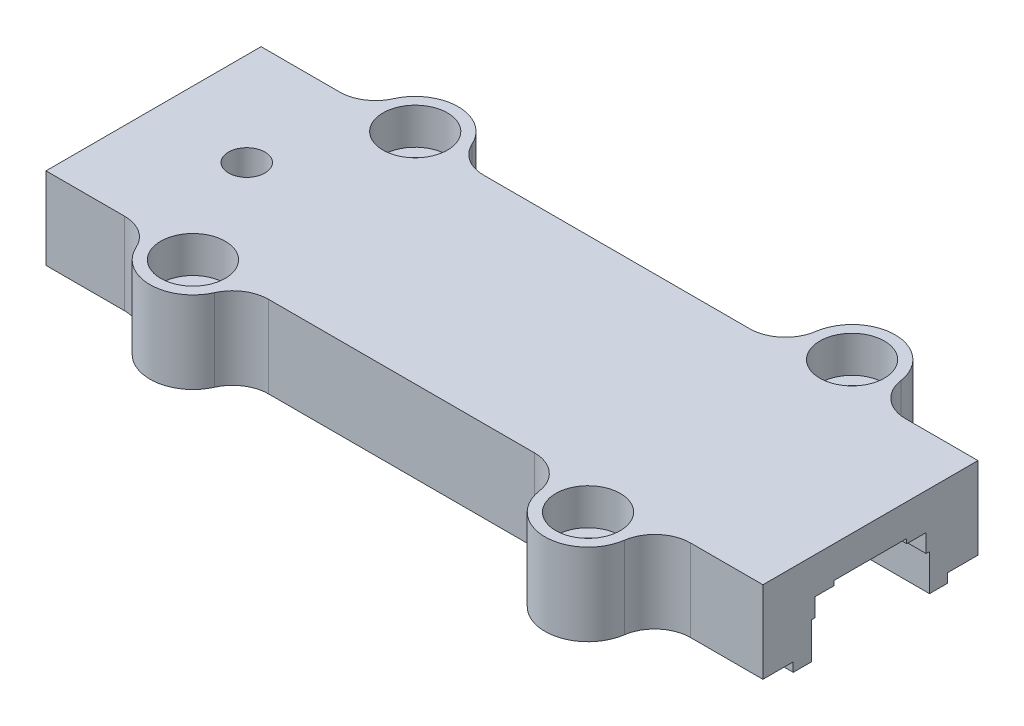
SolidWorks part; units mm, degrees
ref_plane "Front Plane" through (0, 0, 0) normal (0, 0, 1) x (1, 0, 0)
ref_plane "Top Plane" through (0, 0, 0) normal (0, 1, 0) x (1, 0, 0)
ref_plane "Right Plane" through (0, 0, 0) normal (1, 0, 0) x (0, 0, -1)
sketch "Sketch1" plane through (0, 0, 0) normal (0, 1, 0) x (1, 0, 0)
  line L1 (0, 15) -> (100, 15)
  line L2 (0, 15) -> (0, -15)
  line L3 (0, -15) -> (100, -15)
  line L4 (100, 15) -> (100, -15)
  point P4 (0, 0)
  dimension "D1" = 30
  dimension "D2" = 100
extrude "Boss-Extrude1" add sketch "Sketch1" along normal blind 12.7
sketch "Sketch2" plane through (100, 0, 0) normal (1, 0, 0) x (0, 0, -1)
  line L1 (-7.6, 0) -> (7.6, 0)
  line L2 (-7.6, 0) -> (-7.6, 7.62)
  line L3 (-7.6, 7.62) -> (7.6, 7.62)
  line L4 (7.6, 0) -> (7.6, 7.62)
  point P4 (0, 0)
  dimension "D1" = 15.2
  dimension "D2" = 7.62
extrude "Cut-Extrude1" cut sketch "Sketch2" against normal through all
sketch "Sketch3" plane through (100, 0, 0) normal (1, 0, 0) x (0, 0, -1)
  line L1 (-15, 0) -> (-7.6, 0) construction
  line L2 (7.6, 0) -> (15, 0) construction
  line L3 (-7.6, 0) -> (-8.235, 0)
  line L10 (7.6, 0) -> (7.6, 7.62) construction
  line L12 (7.6, 7.62) -> (-7.6, 7.62) construction
  line L13 (-7.6, 0) -> (-8.235, 0)
  line L14 (-7.6, 0) -> (-7.6, 5.08)
  line L15 (-7.6, 5.08) -> (-8.235, 5.08)
  line L16 (-8.235, 0) -> (-8.235, 5.08)
  line L17 (-7.6, 7.62) -> (-7.6, 0) construction
  line L18 (7.6, 0) -> (8.235, 0)
  line L19 (7.6, 0) -> (7.6, 5.08)
  line L20 (7.6, 5.08) -> (8.235, 5.08)
  line L21 (8.235, 0) -> (8.235, 5.08)
  line L22 (-5.06, 7.62) -> (5.06, 7.62)
  line L23 (-5.06, 7.62) -> (-5.06, 8.255)
  line L24 (-5.06, 8.255) -> (5.06, 8.255)
  line L25 (5.06, 7.62) -> (5.06, 8.255)
  line M1 (-15, 0) -> (-7.6, 0)
  line M2 (-7.6, 0) -> (-7.6, 7.62)
  line M3 (-7.6, 7.62) -> (7.6, 7.62)
  line M4 (7.6, 7.62) -> (7.6, 0)
  line M5 (7.6, 0) -> (15, 0)
  dimension "D5" = 0.635
  dimension "D6" = 2.54
  dimension "D7" = 0.635
  dimension "D8" = 2.54
  dimension "D9" = 0.635
  dimension "D10" = 2.54
  dimension "D11" = 2.54
extrude "Cut-Extrude2" cut sketch "Sketch3" against normal through all contours L16 L15 M1 M2 | L25 L24 L23 M3 | L21 L20 M5 M4 region at (100, 2.54, -7.9175) region at (100, 7.9375, 0) region at (100, 2.54, 7.9175)
sketch "Sketch4" plane through (0, 0, 0) normal (0, -1, 0) x (1, 0, 0)
  line L1 (0, -8.235) -> (5, -8.235)
  line L2 (0, -8.235) -> (0, 8.235)
  line L3 (0, 8.235) -> (5, 8.235)
  line L4 (5, -8.235) -> (5, 8.235)
  line L5 (0, -8.235) -> (100, -8.235) construction
  line L6 (0, 8.235) -> (100, 8.235) construction
  dimension "D1" = 5
extrude "Boss-Extrude2" add sketch "Sketch4" against normal up to next
fillet "Fillet7" radius 1.5875 2 edges at (5, 6.35, -7.6) (5, 6.35, 7.6)
fillet "Fillet8" radius 1.5875 2 edges at (5, 2.54, -8.235) (5, 2.54, 8.235)
sketch "Sketch9" plane through (0, 7.62, 0) normal (0, -1, 0) x (1, 0, 0)
  line L0 (5, -5.06) -> (100, -5.06) construction
  line L1 (5, 5.06) -> (24.05, 5.06)
  line L2 (5, 5.06) -> (5, -5.06)
  line L3 (5, -5.06) -> (24.05, -5.06)
  line L4 (24.05, 5.06) -> (24.05, -5.06)
  dimension "D1" = 19.05
extrude "Boss-Extrude3" add sketch "Sketch9" against normal up to next
sketch "Sketch7" plane through (0, 7.62, 0) normal (0, -1, 0) x (1, 0, 0)
  line L0 (0, -15) -> (0, 15) construction
  line L1 (5, -6.0125) -> (5, 6.0125) construction
  circle A0 centre (13, 0) radius 2.54
  point P6 (0, 0)
  dimension "D1" = 5.08
  dimension "D2" = 8
extrude "Cut-Extrude4" cut sketch "Sketch7" against normal through all
sketch "Sketch10" plane through (0, 7.62, 0) normal (0, -1, 0) x (1, 0, 0)
  circle A0 centre (13, 0) radius 3.429
  circle A3 centre (13, 0) radius 2.54 construction
  dimension "D1" = 6.858
extrude "Cut-Extrude6" cut sketch "Sketch10" against normal blind 1.27
fillet "Fillet5" radius 1.5875 2 edges at (24.05, 7.9375, -5.06) (24.05, 7.9375, 5.06)
sketch "Sketch11" plane through (0, 12.7, 0) normal (0, 1, 0) x (1, 0, 0)
  line L0 (73, -15) -> (73.0221, -18.415)
  line L1 (85, -15) -> (85.0221, -18.415)
  line L4 (27, -15.5) -> (27, -15)
  line L5 (15, -15) -> (15, -15.5)
  line L8 (15, -15) -> (27, -15)
  line L9 (73, -15) -> (85, -15)
  line L11 (0, 15) -> (0, -15) construction
  line L13 (0, -15) -> (100, -15) construction
  arc A0 (73.0847, -19.2795) -> (84.9594, -19.2795) centre (79.0221, -18.415) ccw construction
  arc A2 (15, -15.5) -> (27, -15.5) centre (21, -15.5) ccw
  arc A3 (73.0221, -18.415) -> (85.0221, -18.415) centre (79.0221, -18.415) ccw
  dimension "D1" = 15
  dimension "D2" = 12
  dimension "D4" = 12
  dimension "D5" = 0.5
extrude "Boss-Extrude4" add sketch "Sketch11" against normal up to surface (12.7 mm away) up to face at (42.2517, 0, 0)
sketch "Sketch12" plane through (0, 12.7, 0) normal (0, 1, 0) x (1, 0, 0)
  circle A0 centre (21, -15.5) radius 4.5
  circle A1 centre (79.0221, -18.415) radius 4.5
  dimension "D1" = 9
extrude "Cut-Extrude7" cut sketch "Sketch12" against normal blind 5.08
sketch "Sketch13" plane through (0, 7.62, 0) normal (0, 1, 0) x (1, 0, 0)
  circle A0 centre (21, -15.5) radius 2.75
  circle A1 centre (79.0221, -18.415) radius 2.75
  dimension "D1" = 5.5
extrude "Cut-Extrude8" cut sketch "Sketch13" against normal through all
mirror "Mirror1" about plane through (0, 0, 0) normal (0, 0, 1) of "Boss-Extrude4", "Cut-Extrude7", "Cut-Extrude8"
fillet "Fillet6" radius 5 8 edges at (73, 6.35, 15) (85, 6.35, 15) (85, 6.35, -15) (73, 6.35, -15)
sketch "Sketch24" plane through (0, 0, 0) normal (0, -1, 0) x (1, 0, 0)
  line L0 (100, -10.775) -> (6.5875, -10.775)
  line L1 (2.46, -6.6475) -> (2.46, 6.6475)
  line L2 (6.5875, 10.775) -> (100, 10.775)
  line L12 (100, -15) -> (100, -8.235)
  line L13 (100, -8.235) -> (6.5875, -8.235)
  line L14 (5, -6.6475) -> (5, 6.6475)
  line L15 (6.5875, 8.235) -> (100, 8.235)
  line L16 (100, 8.235) -> (100, 15)
  line L17 (100, 15) -> (89.9073, 15)
  line L18 (68.1369, 15) -> (31.0374, 15)
  line L19 (10.9626, 15) -> (0, 15)
  line L20 (0, 15) -> (0, -15)
  line L21 (0, -15) -> (10.9626, -15)
  line L22 (31.0374, -15) -> (68.1369, -15)
  line L23 (89.9073, -15) -> (100, -15)
  line L24 (100, -15) -> (100, -10.775)
  line L25 (100, -8.235) -> (6.5875, -8.235) construction
  line L26 (5, -6.6475) -> (5, 6.6475) construction
  line L27 (6.5875, 8.235) -> (100, 8.235) construction
  line L28 (100, 10.775) -> (100, 15)
  line L29 (100, 15) -> (89.9073, 15)
  line L30 (68.1369, 15) -> (31.0374, 15)
  line L31 (10.9626, 15) -> (0, 15)
  line L32 (0, 15) -> (0, -15)
  line L33 (0, -15) -> (10.9626, -15)
  line L34 (31.0374, -15) -> (68.1369, -15)
  line L35 (89.9073, -15) -> (100, -15)
  arc A0 (2.46, -6.6475) -> (6.5875, -10.775) centre (6.5875, -6.6475) ccw
  arc A1 (6.5875, 10.775) -> (2.46, 6.6475) centre (6.5875, 6.6475) ccw
  arc A14 (5, -6.6475) -> (6.5875, -8.235) centre (6.5875, -6.6475) ccw
  arc A15 (6.5875, 8.235) -> (5, 6.6475) centre (6.5875, 6.6475) ccw
  arc A16 (84.9594, 19.2795) -> (89.9073, 15) centre (89.9073, 20) ccw
  arc A17 (84.9594, 19.2795) -> (73.0847, 19.2795) centre (79.0221, 18.415) ccw
  arc A18 (68.1369, 15) -> (73.0847, 19.2795) centre (68.1369, 20) ccw
  arc A19 (26.475, 17.9545) -> (31.0374, 15) centre (31.0374, 20) ccw
  arc A20 (26.475, 17.9545) -> (15.525, 17.9545) centre (21, 15.5) ccw
  arc A21 (10.9626, 15) -> (15.525, 17.9545) centre (10.9626, 20) ccw
  arc A22 (15.525, -17.9545) -> (10.9626, -15) centre (10.9626, -20) ccw
  arc A23 (15.525, -17.9545) -> (26.475, -17.9545) centre (21, -15.5) ccw
  arc A24 (31.0374, -15) -> (26.475, -17.9545) centre (31.0374, -20) ccw
  arc A25 (73.0847, -19.2795) -> (68.1369, -15) centre (68.1369, -20) ccw
  arc A26 (73.0847, -19.2795) -> (84.9594, -19.2795) centre (79.0221, -18.415) ccw
  arc A27 (89.9073, -15) -> (84.9594, -19.2795) centre (89.9073, -20) ccw
  arc A28 (5, -6.6475) -> (6.5875, -8.235) centre (6.5875, -6.6475) ccw construction
  arc A29 (6.5875, 8.235) -> (5, 6.6475) centre (6.5875, 6.6475) ccw construction
  arc A30 (84.9594, 19.2795) -> (89.9073, 15) centre (89.9073, 20) ccw
  arc A31 (84.9594, 19.2795) -> (73.0847, 19.2795) centre (79.0221, 18.415) ccw
  arc A32 (68.1369, 15) -> (73.0847, 19.2795) centre (68.1369, 20) ccw
  arc A33 (26.475, 17.9545) -> (31.0374, 15) centre (31.0374, 20) ccw
  arc A34 (26.475, 17.9545) -> (15.525, 17.9545) centre (21, 15.5) ccw
  arc A35 (10.9626, 15) -> (15.525, 17.9545) centre (10.9626, 20) ccw
  arc A36 (15.525, -17.9545) -> (10.9626, -15) centre (10.9626, -20) ccw
  arc A37 (15.525, -17.9545) -> (26.475, -17.9545) centre (21, -15.5) ccw
  arc A38 (31.0374, -15) -> (26.475, -17.9545) centre (31.0374, -20) ccw
  arc A39 (73.0847, -19.2795) -> (68.1369, -15) centre (68.1369, -20) ccw
  arc A40 (73.0847, -19.2795) -> (84.9594, -19.2795) centre (79.0221, -18.415) ccw
  arc A41 (89.9073, -15) -> (84.9594, -19.2795) centre (89.9073, -20) ccw
  dimension "D3" = 21.55
  dimension "D1" = 0
  dimension "D2" = 2.54
extrude "Cut-Extrude9" cut sketch "Sketch24" against normal blind 1.27
sketch "Sketch25" plane through (0, 7.62, 0) normal (0, -1, 0) x (1, 0, 0)
  line L0 (27.86, 6.3669) -> (27.86, 0.436) construction
  line L1 (5, -6.6475) -> (5, 6.6475) construction
  line L2 (6.5875, 7.6) -> (100, 7.6) construction
  line L3 (24.685, 7.6) -> (27.86, 7.6)
  line L4 (24.685, 7.6) -> (24.685, 5.06)
  line L5 (24.685, 5.06) -> (27.86, 5.06)
  line L6 (27.86, 7.6) -> (27.86, 5.06)
  line L7 (25.6375, 5.06) -> (100, 5.06) construction
  line L8 (6.5875, -7.6) -> (100, -7.6) construction
  line L9 (24.685, -7.6) -> (27.86, -7.6)
  line L10 (24.685, -7.6) -> (24.685, -5.06)
  line L11 (24.685, -5.06) -> (27.86, -5.06)
  line L12 (27.86, -7.6) -> (27.86, -5.06)
  line L13 (25.6375, -5.06) -> (100, -5.06) construction
  dimension "D1" = 22.86
  dimension "D2" = 3.175
extrude "Boss-Extrude5" add sketch "Sketch25" along normal blind 2.54
sketch "Sketch26" plane through (24.685, 0, 0) normal (-1, 0, 0) x (0, 0, 1)
  line L0 (7.6, 7.62) -> (5.06, 7.62) construction
  line L1 (5.06, 7.62) -> (5.06, 5.08) construction
  line L2 (5.06, 5.08) -> (7.6, 5.08) construction
  line L3 (7.6, 5.08) -> (7.6, 7.62) construction
  line L4 (-5.06, 7.62) -> (-7.6, 7.62) construction
  line L5 (-7.6, 7.62) -> (-7.6, 5.08) construction
  line L6 (-7.6, 5.08) -> (-5.06, 5.08) construction
  line L7 (-5.06, 5.08) -> (-5.06, 7.62) construction
  line L8 (7.6, 7.62) -> (5.06, 7.62)
  line L9 (5.06, 7.62) -> (5.06, 5.08)
  line L10 (5.06, 5.08) -> (7.6, 5.08)
  line L11 (7.6, 5.08) -> (7.6, 7.62)
  line L12 (-5.06, 7.62) -> (-7.6, 7.62)
  line L13 (-7.6, 7.62) -> (-7.6, 5.08)
  line L14 (-7.6, 5.08) -> (-5.06, 5.08)
  line L15 (-5.06, 5.08) -> (-5.06, 7.62)
extrude "Boss-Extrude6" add sketch "Sketch26" along normal up to next
sketch "Sketch31" plane through (100, 0, 0) normal (1, 0, 0) x (0, 0, -1)
  line L2 (7.6, 5.08) -> (7.7651, 5.08)
  line L3 (7.6, 5.08) -> (7.6, 7.62)
  line L4 (7.6, 7.62) -> (7.7651, 7.62)
  line L5 (7.7651, 5.08) -> (7.7651, 7.62)
  line L6 (-7.6, 5.08) -> (-7.7651, 5.08)
  line L7 (-7.6, 5.08) -> (-7.6, 7.62)
  line L8 (-7.6, 7.62) -> (-7.7651, 7.62)
  line L9 (-7.7651, 5.08) -> (-7.7651, 7.62)
  dimension "D1" = 0.1651
  dimension "D2" = 0.1651
extrude "adjust" cut sketch "Sketch31" against normal up to surface (72.14 mm away) up to face at (27.86, 6.35, -6.33)
fillet "Fillet9" radius 1.5875 4 edges at (5, 6.35, -5.06) (5, 6.35, 5.06) (27.86, 6.35, 7.7651) (27.86, 6.35, -7.7651)
sketch "Sketch27" plane through (0, 0, 0) normal (0, 1, 0) x (1, 0, 0)
  line L1 (-5.3987, 25.4) -> (108.9013, 25.4)
  line L2 (-5.3987, 25.4) -> (-5.3987, -25.4)
  line L3 (-5.3987, -25.4) -> (108.9013, -25.4)
  line L4 (108.9013, 25.4) -> (108.9013, -25.4)
  point P4 (-5.3987, 0)
  dimension "D1" = 50.8
  dimension "D2" = 114.3
sketch "Sketch28" plane through (0, 0, 0) normal (0, -1, 0) x (1, 0, 0)
  line L0 (0, 0) -> (-2.8235, 0) construction
sketch "Sketch29" plane through (0, 12.7, 0) normal (0, 1, 0) x (1, 0, 0)
  line L8 (0, 15) -> (0, -15)
  line L9 (0, -15) -> (10.9626, -15)
  line L10 (31.0374, -15) -> (68.1369, -15)
  line L11 (89.9073, -15) -> (100, -15)
  line L12 (100, -15) -> (100, 15)
  line L13 (100, 15) -> (89.9073, 15)
  line L14 (68.1369, 15) -> (31.0374, 15)
  line L15 (10.9626, 15) -> (0, 15)
  line L16 (0, 15) -> (0, -15)
  line L17 (0, -15) -> (10.9626, -15)
  line L18 (31.0374, -15) -> (68.1369, -15)
  line L19 (89.9073, -15) -> (100, -15)
  line L20 (100, -15) -> (100, 15)
  line L21 (100, 15) -> (89.9073, 15)
  line L22 (68.1369, 15) -> (31.0374, 15)
  line L23 (10.9626, 15) -> (0, 15)
  arc A12 (15.525, -17.9545) -> (10.9626, -15) centre (10.9626, -20) ccw
  arc A13 (15.525, -17.9545) -> (26.475, -17.9545) centre (21, -15.5) ccw
  arc A14 (31.0374, -15) -> (26.475, -17.9545) centre (31.0374, -20) ccw
  arc A15 (73.0847, -19.2795) -> (68.1369, -15) centre (68.1369, -20) ccw
  arc A16 (73.0847, -19.2795) -> (84.9594, -19.2795) centre (79.0221, -18.415) ccw
  arc A17 (89.9073, -15) -> (84.9594, -19.2795) centre (89.9073, -20) ccw
  arc A18 (84.9594, 19.2795) -> (89.9073, 15) centre (89.9073, 20) ccw
  arc A19 (84.9594, 19.2795) -> (73.0847, 19.2795) centre (79.0221, 18.415) ccw
  arc A20 (68.1369, 15) -> (73.0847, 19.2795) centre (68.1369, 20) ccw
  arc A21 (26.475, 17.9545) -> (31.0374, 15) centre (31.0374, 20) ccw
  arc A22 (26.475, 17.9545) -> (15.525, 17.9545) centre (21, 15.5) ccw
  arc A23 (10.9626, 15) -> (15.525, 17.9545) centre (10.9626, 20) ccw
  arc A24 (15.525, -17.9545) -> (10.9626, -15) centre (10.9626, -20) ccw
  arc A25 (15.525, -17.9545) -> (26.475, -17.9545) centre (21, -15.5) ccw
  arc A26 (31.0374, -15) -> (26.475, -17.9545) centre (31.0374, -20) ccw
  arc A27 (73.0847, -19.2795) -> (68.1369, -15) centre (68.1369, -20) ccw
  arc A28 (73.0847, -19.2795) -> (84.9594, -19.2795) centre (79.0221, -18.415) ccw
  arc A29 (89.9073, -15) -> (84.9594, -19.2795) centre (89.9073, -20) ccw
  arc A30 (84.9594, 19.2795) -> (89.9073, 15) centre (89.9073, 20) ccw
  arc A31 (84.9594, 19.2795) -> (73.0847, 19.2795) centre (79.0221, 18.415) ccw
  arc A32 (68.1369, 15) -> (73.0847, 19.2795) centre (68.1369, 20) ccw
  arc A33 (26.475, 17.9545) -> (31.0374, 15) centre (31.0374, 20) ccw
  arc A34 (26.475, 17.9545) -> (15.525, 17.9545) centre (21, 15.5) ccw
  arc A35 (10.9626, 15) -> (15.525, 17.9545) centre (10.9626, 20) ccw
  dimension "D1" = 0
sketch "Sketch30" plane through (0, 12.7, 0) normal (0, 1, 0) x (1, 0, 0)
  line L0 (100, 3.2852) -> (100, 15)
  line L1 (0, 15) -> (0, -15) construction
  line L3 (0, -3.0648) -> (0, -15)
  line L4 (46.1739, 15) -> (31.0374, 15)
  line L6 (52.5239, -15) -> (68.1369, -15)
  line L8 (0, 15) -> (0, -15)
  line L9 (0, -15) -> (10.9626, -15)
  line L10 (31.0374, -15) -> (68.1369, -15)
  line L11 (89.9073, -15) -> (100, -15)
  line L12 (100, -15) -> (100, 15)
  line L13 (100, 15) -> (89.9073, 15)
  line L14 (68.1369, 15) -> (31.0374, 15)
  line L15 (10.9626, 15) -> (0, 15)
  line L16 (0, 15) -> (0, 3.2852)
  line L17 (0, -15) -> (10.9626, -15)
  line L18 (31.0374, -15) -> (46.1739, -15)
  line L19 (89.9073, -15) -> (100, -15)
  line L20 (100, -15) -> (100, -3.0648)
  line L21 (100, 15) -> (89.9073, 15)
  line L22 (68.1369, 15) -> (52.5239, 15)
  line L23 (10.9626, 15) -> (0, 15)
  arc A12 (15.525, -17.9545) -> (10.9626, -15) centre (10.9626, -20) ccw
  arc A13 (15.525, -17.9545) -> (26.475, -17.9545) centre (21, -15.5) ccw
  arc A14 (31.0374, -15) -> (26.475, -17.9545) centre (31.0374, -20) ccw
  arc A15 (73.0847, -19.2795) -> (68.1369, -15) centre (68.1369, -20) ccw
  arc A16 (73.0847, -19.2795) -> (84.9594, -19.2795) centre (79.0221, -18.415) ccw
  arc A17 (89.9073, -15) -> (84.9594, -19.2795) centre (89.9073, -20) ccw
  arc A18 (84.9594, 19.2795) -> (89.9073, 15) centre (89.9073, 20) ccw
  arc A19 (84.9594, 19.2795) -> (73.0847, 19.2795) centre (79.0221, 18.415) ccw
  arc A20 (68.1369, 15) -> (73.0847, 19.2795) centre (68.1369, 20) ccw
  arc A21 (26.475, 17.9545) -> (31.0374, 15) centre (31.0374, 20) ccw
  arc A22 (26.475, 17.9545) -> (15.525, 17.9545) centre (21, 15.5) ccw
  arc A23 (10.9626, 15) -> (15.525, 17.9545) centre (10.9626, 20) ccw
  arc A24 (15.525, -17.9545) -> (10.9626, -15) centre (10.9626, -20) ccw
  arc A25 (15.525, -17.9545) -> (26.475, -17.9545) centre (21, -15.5) ccw
  arc A26 (31.0374, -15) -> (26.475, -17.9545) centre (31.0374, -20) ccw
  arc A27 (73.0847, -19.2795) -> (68.1369, -15) centre (68.1369, -20) ccw
  arc A28 (73.0847, -19.2795) -> (84.9594, -19.2795) centre (79.0221, -18.415) ccw
  arc A29 (89.9073, -15) -> (84.9594, -19.2795) centre (89.9073, -20) ccw
  arc A30 (84.9594, 19.2795) -> (89.9073, 15) centre (89.9073, 20) ccw
  arc A31 (84.9594, 19.2795) -> (73.0847, 19.2795) centre (79.0221, 18.415) ccw
  arc A32 (68.1369, 15) -> (73.0847, 19.2795) centre (68.1369, 20) ccw
  arc A33 (26.475, 17.9545) -> (31.0374, 15) centre (31.0374, 20) ccw
  arc A34 (26.475, 17.9545) -> (15.525, 17.9545) centre (21, 15.5) ccw
  arc A35 (10.9626, 15) -> (15.525, 17.9545) centre (10.9626, 20) ccw
  dimension "D2" = 6.35
  dimension "D3" = 6.35
  dimension "D1" = 0
sketch "Sketch32" plane through (0, 12.7, 0) normal (0, 1, 0) x (1, 0, 0)
  line L3 (100, -10.775) -> (100, -15) construction
equation "\"D11@Sketch3\"=\"D10@Sketch3\""
equation "\"D6@Sketch3\"=\"D10@Sketch3\""
equation "\"D8@Sketch3\"=\"D10@Sketch3\""
equation "\"D9@Sketch3\" = \"D5@Sketch3\""
equation "\"D7@Sketch3\"=\"D5@Sketch3\""
